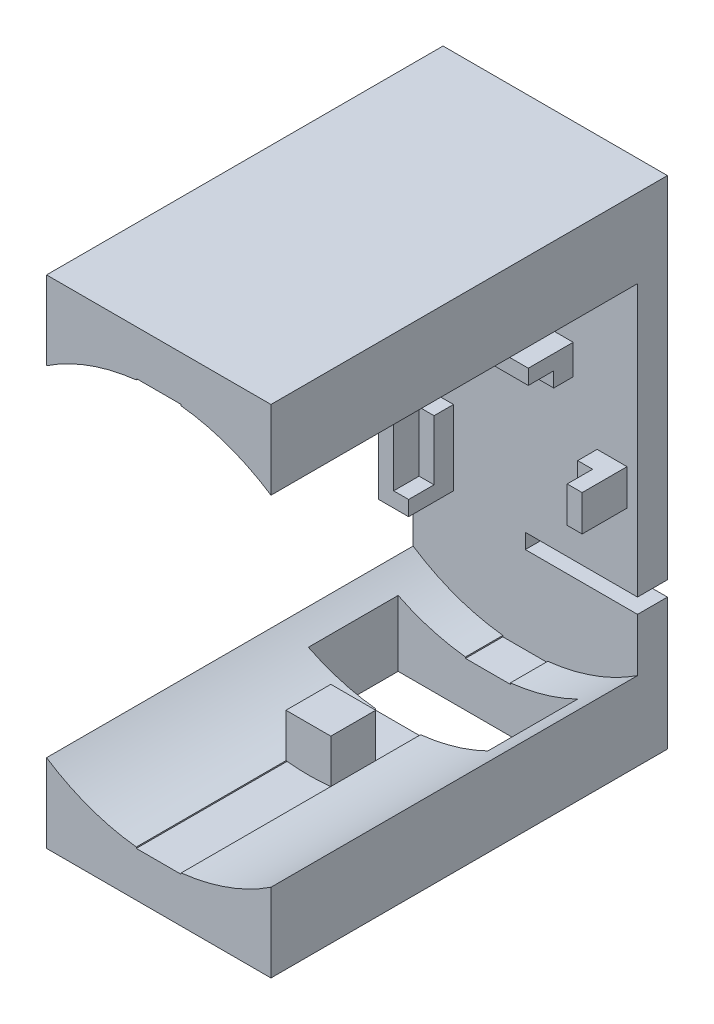
SolidWorks part; units mm, degrees
ref_plane "Front Plane" through (0, 0, 0) normal (0, 0, 1) x (1, 0, 0)
ref_plane "Top Plane" through (0, 0, 0) normal (0, 1, 0) x (1, 0, 0)
ref_plane "Right Plane" through (0, 0, 0) normal (1, 0, 0) x (0, 0, -1)
sketch "Sketch1" plane through (0, 0, 0) normal (0, 0, 1) x (1, 0, 0)
  line L0 (-5.7863, 0) -> (7.2515, 0) construction
  line L1 (-7.5, 16.6) -> (7.5, 16.6)
  line L2 (-7.5, 16.6) -> (-7.5, -16.6)
  line L3 (-7.5, -16.6) -> (7.5, -16.6)
  line L4 (7.5, 16.6) -> (7.5, -16.6)
  line L5 (0, 21.636) -> (0, -26241.9537) construction
  line L7 (-1.5, 13.6) -> (1.5, 13.6)
  line L8 (-1.5, 13.6) -> (-1.5, 10.6)
  line L9 (-1.5, 10.6) -> (1.5, 10.6)
  line L10 (1.5, 13.6) -> (1.5, 10.6)
  line L11 (-1.5, -10.6) -> (1.5, -10.6)
  line L12 (-1.5, -10.6) -> (-1.5, -13.6)
  line L13 (-1.5, -13.6) -> (1.5, -13.6)
  line L14 (1.5, -10.6) -> (1.5, -13.6)
  circle A0 centre (0, 0) radius 13.6
  point P11 (0, 16.6)
  point P12 (0, -16.6)
  point P21 (0, 13.6)
  point P22 (0, -13.6)
  point P23 (-7.5, 0)
  dimension "D1" = 27.2
  dimension "D2" = 3
  dimension "D3" = 3
  dimension "D4" = 15
extrude "Boss-Extrude1" add sketch "Sketch1" along normal blind 14.5 contours A0 L4 L1 L2 L8 L7 L10 | L10 A0 L8 L9 | L12 A0 L14 L11 | A0 L2 L3 L4 L14 L13 L12 region at (0, 14.6802, 0) region at (0, -14.6802, 0) region at (0, 12.0863, 0) region at (0, -12.0863, 0)
extrude "Boss-Extrude3" add sketch "Sketch1<3>" against normal blind 2 contours L4 A0 L10 L9 L8 L2 L12 L11 L14 | A0 L4 L1 L2 L8 L7 L10 | A0 L2 L3 L4 L14 L13 L12 | L8 L7 L10 L9 | L12 L11 L14 L13 region at (0, 14.6802, 0) region at (0, 0, 0) region at (0, -14.6802, 0)
sketch "Sketch1<3>" plane through (0, 0, 0) normal (0, 0, 1) x (1, 0, 0) same geometry as "Sketch1"
extrude "Cut-Extrude1" cut sketch "Sketch1<4>" along normal offset from surface (11.5 mm away) 3 contours L12 A0 L14 L11 | L10 A0 L8 L9 region at (0, 12.0863, 0) region at (0, -12.0863, 0) up to face at (0, -12.0793, 14.5)
sketch "Sketch1<4>" plane through (0, 0, 0) normal (0, 0, 1) x (1, 0, 0) same geometry as "Sketch1"
extrude "Boss-Extrude4" add sketch "Sketch1<5>" along normal offset from surface (24.5 mm away) 10 contours A0 L4 L1 L2 L8 L7 L10 | A0 L2 L3 L4 L14 L13 L12 region at (0, 14.6802, 0) region at (0, -14.6802, 0) up to face at (0, 13.8547, 14.5) offset beyond the face yes
sketch "Sketch1<5>" plane through (0, 0, 0) normal (0, 0, 1) x (1, 0, 0) same geometry as "Sketch1"
sketch "Sketch2" plane through (0, 0, 0) normal (0, 0, 1) x (1, 0, 0)
  line L0 (0, 0) -> (50000, 0) construction
  line L1 (-3.2, 5.8) -> (3.2, 5.8)
  line L2 (-3.2, 5.8) -> (-3.2, 4.8)
  line L3 (-3.2, 4.8) -> (3.2, 4.8)
  line L4 (3.2, 5.8) -> (3.2, 4.8)
  line L5 (-6.8, -1.8) -> (-4.8, -1.8)
  line L6 (-6.8, -1.8) -> (-6.8, -6.8)
  line L7 (-6.8, -6.8) -> (-4.8, -6.8)
  line L8 (-4.8, -1.8) -> (-4.8, -6.8)
  line L9 (-4.8, -1.8) -> (-5.8, -1.8)
  line L10 (-4.8, -1.8) -> (-4.8, -5.8)
  line L11 (-4.8, -5.8) -> (-5.8, -5.8)
  line L12 (-5.8, -1.8) -> (-5.8, -5.8)
  line L13 (6.8, 0.4) -> (4.8, 0.4)
  line L14 (6.8, 0.4) -> (6.8, -2)
  line L15 (6.8, -2) -> (4.8, -2)
  line L16 (4.8, 0.4) -> (4.8, -2)
  line L17 (6.8, 0.4) -> (5.8, 0.4)
  line L18 (6.8, 0.4) -> (6.8, -2)
  line L19 (6.8, -2) -> (5.8, -2)
  line L20 (5.8, 0.4) -> (5.8, -2)
  line L21 (-3.2, 5.8) -> (3.2, 5.8)
  line L22 (-3.2, 5.8) -> (-3.2, 3.8)
  line L23 (-3.2, 3.8) -> (3.2, 3.8)
  line L24 (3.2, 5.8) -> (3.2, 3.8)
  line L25 (0, 0) -> (0, 50000) construction
  line L26 (7.5, 11.345) -> (7.5, -11.345) construction
  line L27 (7.5, -6.8) -> (0, -6.8)
  line L28 (7.5, -6.8) -> (7.5, -7.8)
  line L29 (7.5, -7.8) -> (0, -7.8)
  line L30 (0, -6.8) -> (0, -7.8)
  point P24 (0, 3.8)
  point P25 (-5.8, -1.8)
  dimension "D1" = 4.8
  dimension "D2" = 6.4
  dimension "D3" = 1
  dimension "D4" = 1
  dimension "D5" = 0.4
  dimension "D6" = 2
  dimension "D7" = 1
  dimension "D8" = 1
  dimension "D9" = 5.8
  dimension "D10" = 5.8
  dimension "D11" = 1
  dimension "D12" = 1
  dimension "D13" = 5.8
  dimension "D14" = 1
  dimension "D15" = 4
  dimension "D17" = 1
extrude "Boss-Extrude5" add sketch "Sketch2" along normal blind 1.3 contours L5 L12 L11 L8 | L24 L3 L22 L23 | L20 L13 L16 L15 region at (0, 4.3, 0) region at (-5.3, -3.8, 0) region at (5.3, -0.8, 0)
extrude "Boss-Extrude6" add sketch "Sketch2<3>" along normal blind 3 contours L4 L1 L2 L3 | L12 L5 L6 L7 L8 L11 | L13 L20 L15 L14 region at (0, 5.3, 0) region at (-6.1333, -4.6333, 0) region at (6.3, -0.8, 0)
sketch "Sketch2<3>" plane through (0, 0, 0) normal (0, 0, 1) x (1, 0, 0) same geometry as "Sketch2"
extrude "Cut-Extrude2" cut sketch "Sketch2<4>" against normal through all contours L27 L30 L29 L28 region at (3.75, -7.3, 0)
sketch "Sketch2<4>" plane through (0, 0, 0) normal (0, 0, 1) x (1, 0, 0) same geometry as "Sketch2"
ref_plane "Plane1" through (0, -11.345, 0) normal (0, -1, 0) x (-1, 0, 0)
sketch "Sketch3" plane through (0, -11.345, 0) normal (0, -1, 0) x (-1, 0, 0)
  line L1 (6, -2.5) -> (-6, -2.5)
  line L2 (6, -2.5) -> (6, -8.5)
  line L3 (6, -8.5) -> (-6, -8.5)
  line L4 (-6, -2.5) -> (-6, -8.5)
  line L6 (1.5, -24.5) -> (-1.5, -24.5) construction
  line L7 (1.5, 0) -> (-1.5, 0) construction
  point P4 (6.4705, -7.7147)
  point P5 (-5.05, -7.2653)
  point P8 (0, -24.5)
  point P10 (0, -8.5)
  dimension "D1" = 6
  dimension "D2" = 12
  dimension "D3" = 2.5
extrude "Cut-Extrude4" cut sketch "Sketch3" along normal up to surface (5.255 mm away) up to face at (0, -16.6, 11.25)
